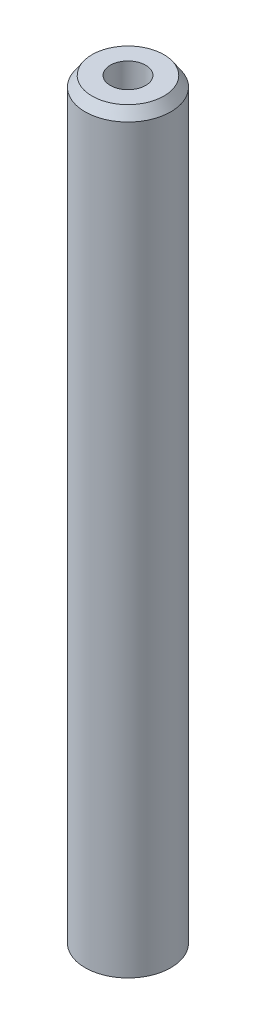
SolidWorks part; units mm, degrees
ref_plane "Front Plane" through (0, 0, 0) normal (0, 0, 1) x (1, 0, 0)
ref_plane "Top Plane" through (0, 0, 0) normal (0, 1, 0) x (1, 0, 0)
ref_plane "Right Plane" through (0, 0, 0) normal (1, 0, 0) x (0, 0, -1)
sketch "Sketch1" plane through (0, 0, 0) normal (0, 1, 0) x (1, 0, 0)
  circle A0 centre (0, 0) radius 5
  dimension "SHAFT_OD" = 10
extrude "Boss-Extrude1" add sketch "Sketch1" along normal blind 88.4882
sketch "Sketch2" plane through (0, 0, 0) normal (0, 1, 0) x (1, 0, 0)
  circle A0 centre (0, 0) radius 2.0586
  dimension "BORE_D" = 4.1172
extrude "Cut-Extrude1" cut sketch "Sketch2" along normal through all
chamfer "Chamfer1" distance 1.188 angle 34.218 2 edges at (0, 88.4882, 5) (0, 0, 5) first distance on face at (0, 88.4882, 5) first distance on face at (0, 0, 2.0586)
